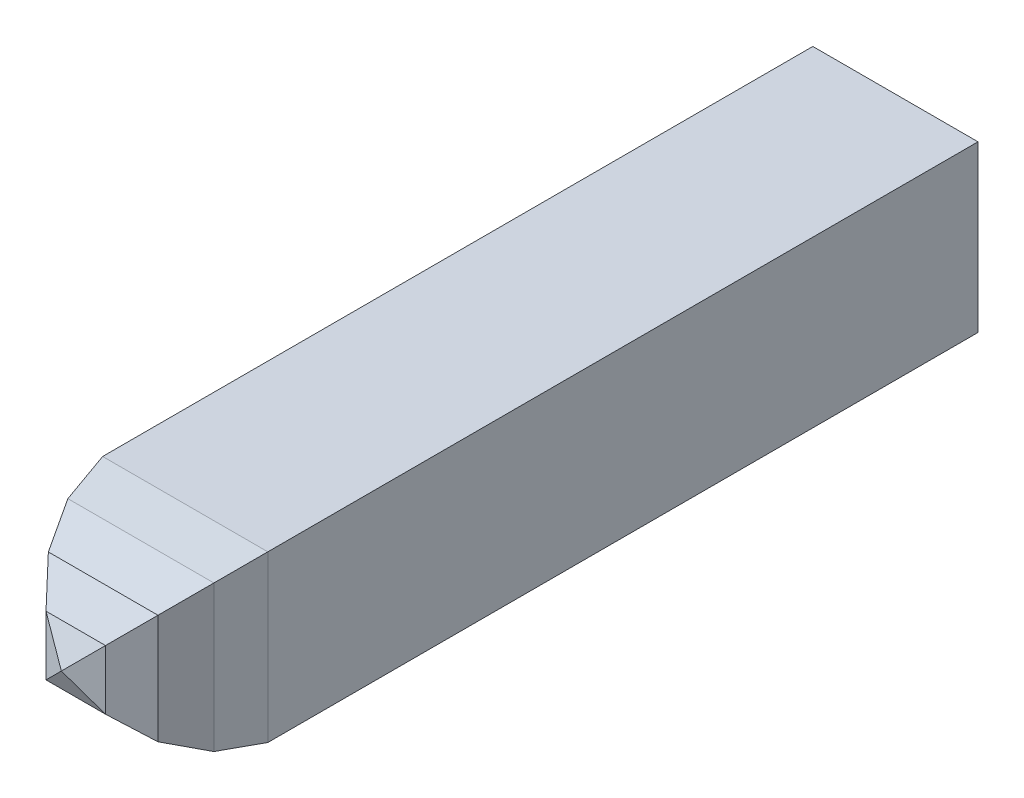
SolidWorks part; units mm, degrees
ref_plane "Front Plane" through (0, 0, 0) normal (0, 0, 1) x (1, 0, 0)
ref_plane "Top Plane" through (0, 0, 0) normal (0, 1, 0) x (1, 0, 0)
ref_plane "Right Plane" through (0, 0, 0) normal (1, 0, 0) x (0, 0, -1)
sketch "Sketch1" plane through (0, 0, 0) normal (0, 0, 1) x (1, 0, 0)
  line L1 (-50.8, -50.8) -> (50.8, -50.8)
  line L2 (-50.8, -50.8) -> (-50.8, 50.8)
  line L3 (-50.8, 50.8) -> (50.8, 50.8)
  line L4 (50.8, -50.8) -> (50.8, 50.8)
  line L5 (-50.8, -50.8) -> (50.8, 50.8) construction
  line L6 (-50.8, 50.8) -> (50.8, -50.8) construction
  point P0 (0, 0)
  dimension "D1" = 101.6
  dimension "D2" = 101.6
extrude "Boss-Extrude1" add sketch "Sketch1" along normal blind 436.88 contours L2 L1 L4 L3
ref_plane "Plane1" through (0, 0, 464.1566) normal (0, 0, 1) x (1, 0, 0)
sketch "Sketch3" plane through (0, 0, 464.1566) normal (0, 0, 1) x (1, 0, 0)
  line L1 (-44.9132, -44.9132) -> (44.9132, -44.9132)
  line L2 (-44.9132, -44.9132) -> (-44.9132, 44.9132)
  line L3 (-44.9132, 44.9132) -> (44.9132, 44.9132)
  line L4 (44.9132, -44.9132) -> (44.9132, 44.9132)
  line L5 (-44.9132, -44.9132) -> (44.9132, 44.9132) construction
  line L6 (-44.9132, 44.9132) -> (44.9132, -44.9132) construction
  point P0 (0, 0)
  dimension "D1" = 89.8265
  dimension "D2" = 89.8265
sketch "Sketch5" plane through (0, 0, 436.88) normal (0, 0, 1) x (1, 0, 0)
  line L0 (50.8, -50.8) -> (50.8, 50.8) construction
  line L1 (-50.8, 50.8) -> (50.8, 50.8) construction
  line L2 (-50.8, -50.8) -> (-50.8, 50.8) construction
  line L3 (-50.8, -50.8) -> (50.8, -50.8) construction
  line L4 (50.8, -50.8) -> (50.8, 50.8)
  line L5 (-50.8, 50.8) -> (50.8, 50.8)
  line L6 (-50.8, -50.8) -> (-50.8, 50.8)
  line L7 (-50.8, -50.8) -> (50.8, -50.8)
loft "Loft2" add profiles "Sketch5", "Sketch3" connector at (-50.8, 50.8, 436.88) connector at (-44.9132, 44.9132, 464.1566)
ref_plane "Plane2" through (0, 0, 487.3594) normal (0, 0, 1) x (1, 0, 0)
sketch "Sketch6" plane through (0, 0, 487.3594) normal (0, 0, 1) x (1, 0, 0)
  line L1 (-33.7159, -33.7159) -> (33.7159, -33.7159)
  line L2 (-33.7159, -33.7159) -> (-33.7159, 33.7159)
  line L3 (-33.7159, 33.7159) -> (33.7159, 33.7159)
  line L4 (33.7159, -33.7159) -> (33.7159, 33.7159)
  line L5 (-33.7159, -33.7159) -> (33.7159, 33.7159) construction
  line L6 (-33.7159, 33.7159) -> (33.7159, -33.7159) construction
  point P0 (0, 0)
  dimension "D1" = 67.4318
  dimension "D2" = 67.4318
loft "Loft3" add profiles "Sketch3<6>", "Sketch6" connector at (-44.9132, 44.9132, 464.1566) connector at (-33.7159, 33.7159, 487.3594)
sketch "Sketch3<6>" plane through (0, 0, 464.1566) normal (0, 0, 1) x (1, 0, 0) same geometry as "Sketch3"
ref_plane "Plane3" through (0, 0, 504.2173) normal (0, 0, 1) x (1, 0, 0)
sketch "Sketch7" plane through (0, 0, 504.2173) normal (0, 0, 1) x (1, 0, 0)
  line L5 (-44.9132, -44.9132) -> (44.9132, 44.9132) construction
  line L6 (-18.3041, -18.3041) -> (18.3041, -18.3041)
  line L8 (-18.3041, -18.3041) -> (-18.3041, 18.3041)
  line L9 (-18.3041, 18.3041) -> (18.3041, 18.3041)
  line L10 (18.3041, -18.3041) -> (18.3041, 18.3041)
  line L11 (-18.3041, -18.3041) -> (18.3041, 18.3041) construction
  line L12 (-18.3041, 18.3041) -> (18.3041, -18.3041) construction
  point P1 (0, 0)
  dimension "D1" = 36.6083
  dimension "D2" = 36.6083
loft "Loft4" add profiles "Sketch6<4>", "Sketch7" connector at (33.7159, 33.7159, 487.3594) connector at (18.3041, 18.3041, 504.2173)
sketch "Sketch6<4>" plane through (0, 0, 487.3594) normal (0, 0, 1) x (1, 0, 0) same geometry as "Sketch6"
sketch3d "3DSketch1" plane through (0, 0, 0) normal (0, 0, 1) x (1, 0, 0)
  dimension "D1" = 8.8627
sketch "Sketch8" plane through (0, 0, 513.08) normal (0, 0, 1) x (1, 0, 0)
  point P0 (0, 0)
loft "Loft5" add profiles "Sketch8", "Sketch7<5>"
sketch "Sketch7<5>" plane through (0, 0, 504.2173) normal (0, 0, 1) x (1, 0, 0) same geometry as "Sketch7"
shell "Shell1" thickness 1.5875 removed face at (0, 0, 0)
